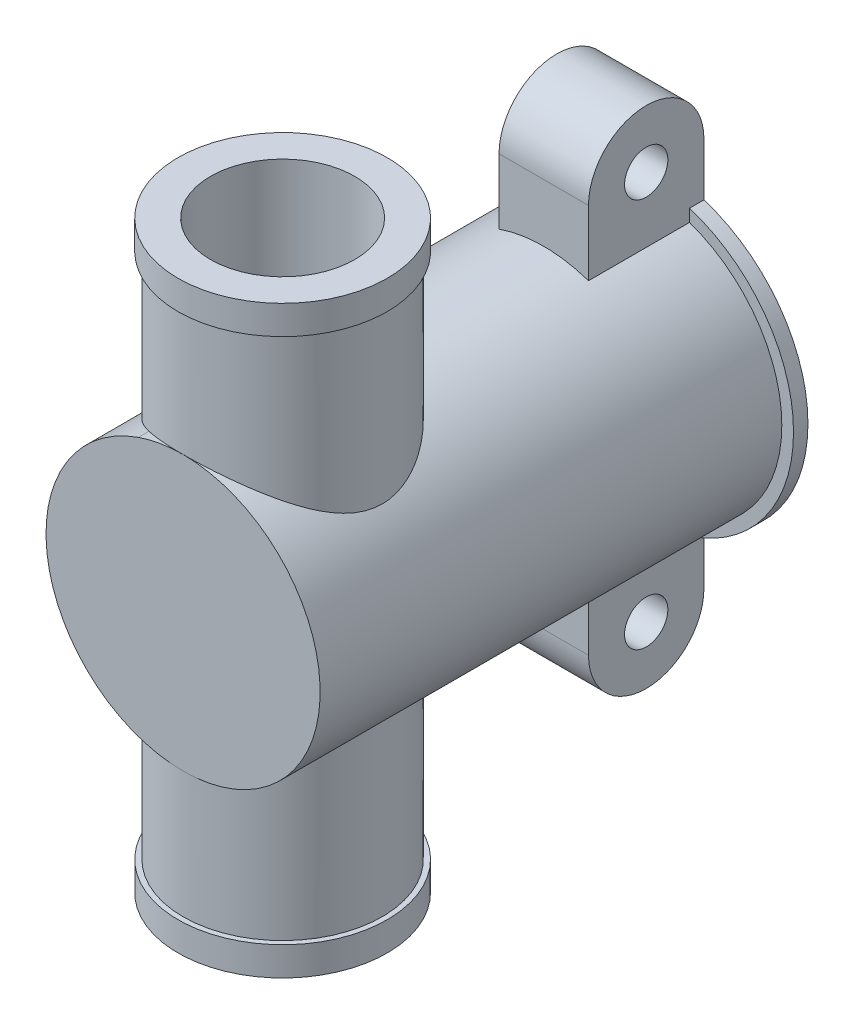
SolidWorks part; units mm, degrees
ref_plane "Front Plane" through (0, 0, 0) normal (0, 0, 1) x (1, 0, 0)
ref_plane "Top Plane" through (0, 0, 0) normal (0, 1, 0) x (1, 0, 0)
ref_plane "Right Plane" through (0, 0, 0) normal (1, 0, 0) x (0, 0, -1)
sketch "Sketch1" plane through (0, 0, 0) normal (0, 0, 1) x (1, 0, 0)
  circle A0 centre (0, 0) radius 9.5
  dimension "D1" = 19
extrude "Boss-Extrude1" add sketch "Sketch1" along normal blind 33
ref_plane "Plane2" through (0, 0, 0) normal (0, 1, 0) x (1, 0, 0)
sketch "Sketch4" plane through (0, 0, 0) normal (0, 1, 0) x (1, 0, 0)
  line L0 (0, -33) -> (0, -19.2) construction
  line L1 (-9.5, -33) -> (9.5, -33) construction
  circle A0 centre (0, -26.1) radius 6.9
  dimension "D1" = 13.8
extrude "Boss-Extrude2" add sketch "Sketch4" against normal up to surface (8.75 mm away) from offset 18.25 up to face at (9.5, 0, 33)
sketch "Sketch5" plane through (0, 0, 0) normal (0, 1, 0) x (1, 0, 0)
  line L0 (0, -33) -> (0, -19.2) construction
  line L1 (-9.5, -33) -> (9.5, -33) construction
  circle A0 centre (0, -26.1) radius 6.9 construction
  circle A1 centre (0, -26.1) radius 6.9
extrude "Boss-Extrude4" add sketch "Sketch5" against normal blind 18.25
sketch "Sketch7" plane through (0, 0, 0) normal (0, 0, -1) x (-1, 0, 0)
  circle A0 centre (0, 0) radius 8
  dimension "D1" = 16
extrude "Cut-Extrude1" cut sketch "Sketch7" against normal blind 28.25
sketch "Sketch8" plane through (0, -18.25, 0) normal (0, -1, 0) x (1, 0, 0)
  line L0 (0, 19.2) -> (0, 33) construction
  circle A0 centre (0, 26.1) radius 6.9 construction
  circle A1 centre (0, 26.1) radius 6.9 construction
  circle A2 centre (0, 26.1) radius 7.25
  dimension "D1" = 14.5
extrude "Boss-Extrude5" add sketch "Sketch8" along normal blind 2
sketch "Sketch9" plane through (0, 18.25, 0) normal (0, 1, 0) x (1, 0, 0)
  line L0 (0, -33) -> (0, -19.2) construction
  circle A0 centre (0, -26.1) radius 6.9 construction
  circle A1 centre (0, -26.1) radius 6.9 construction
  circle A2 centre (0, -26.1) radius 7.25
  dimension "D1" = 14.5
extrude "Boss-Extrude6" add sketch "Sketch9" along normal blind 2
sketch "Sketch10" plane through (0, -20.25, 0) normal (0, -1, 0) x (1, 0, 0)
  line L0 (0, 18.85) -> (0, 33.35) construction
  circle A0 centre (0, 26.1) radius 7.25 construction
  circle A1 centre (0, 26.1) radius 5
  dimension "D1" = 10
extrude "Cut-Extrude3" cut sketch "Sketch10" against normal blind 10
sketch "Sketch11" plane through (0, 20.25, 0) normal (0, 1, 0) x (1, 0, 0)
  line L0 (0, -18.85) -> (0, -33.35) construction
  circle A0 centre (0, -26.1) radius 7.25 construction
  circle A1 centre (0, -26.1) radius 5
  dimension "D1" = 10
extrude "Cut-Extrude4" cut sketch "Sketch11" against normal blind 10
ref_plane "Plane4" through (0, 0, 0) normal (1, 0, 0) x (0, 0, -1)
sketch "Sketch14" plane through (0, 0, 0) normal (1, 0, 0) x (0, 0, -1)
  line L0 (0, 0) -> (-8, 0) construction
  line L1 (0, -9.5) -> (0, 9.5) construction
  line L2 (-8, 13.5) -> (-8, -13.5)
  line L3 (0, 13.5) -> (0, -13.5)
  line L4 (-8, -13.5) -> (0, -13.5) construction
  arc A0 (-8, -13.5) -> (0, -13.5) centre (-4, -13.5) ccw
  arc A1 (-8, 13.5) -> (0, 13.5) centre (-4, 13.5) cw
  circle A2 centre (-4, -13.5) radius 1.5
  circle A3 centre (-4, 13.5) radius 1.5
  dimension "D3" = 3
  dimension "D4" = 3
  dimension "D1" = 8
  dimension "D2" = 13.5
extrude "Boss-Extrude7" add sketch "Sketch14" along normal mid plane 6.2
sketch "Sketch15" plane through (0, 0, 0) normal (0, 0, -1) x (-1, 0, 0)
  circle A0 centre (0, 0) radius 8
extrude "Cut-Extrude5" cut sketch "Sketch15" against normal blind 16.2
sketch "Sketch16" plane through (0, 0, 0) normal (0, 0, -1) x (-1, 0, 0)
  circle A0 centre (0, 0) radius 10.3112
extrude "Boss-Extrude8" add sketch "Sketch16" against normal blind 1
sketch "Sketch17" plane through (0, 0, 0) normal (0, 0, -1) x (-1, 0, 0)
  circle A0 centre (0, 0) radius 8
  dimension "D1" = 16
extrude "Cut-Extrude6" cut sketch "Sketch17" against normal blind 18
